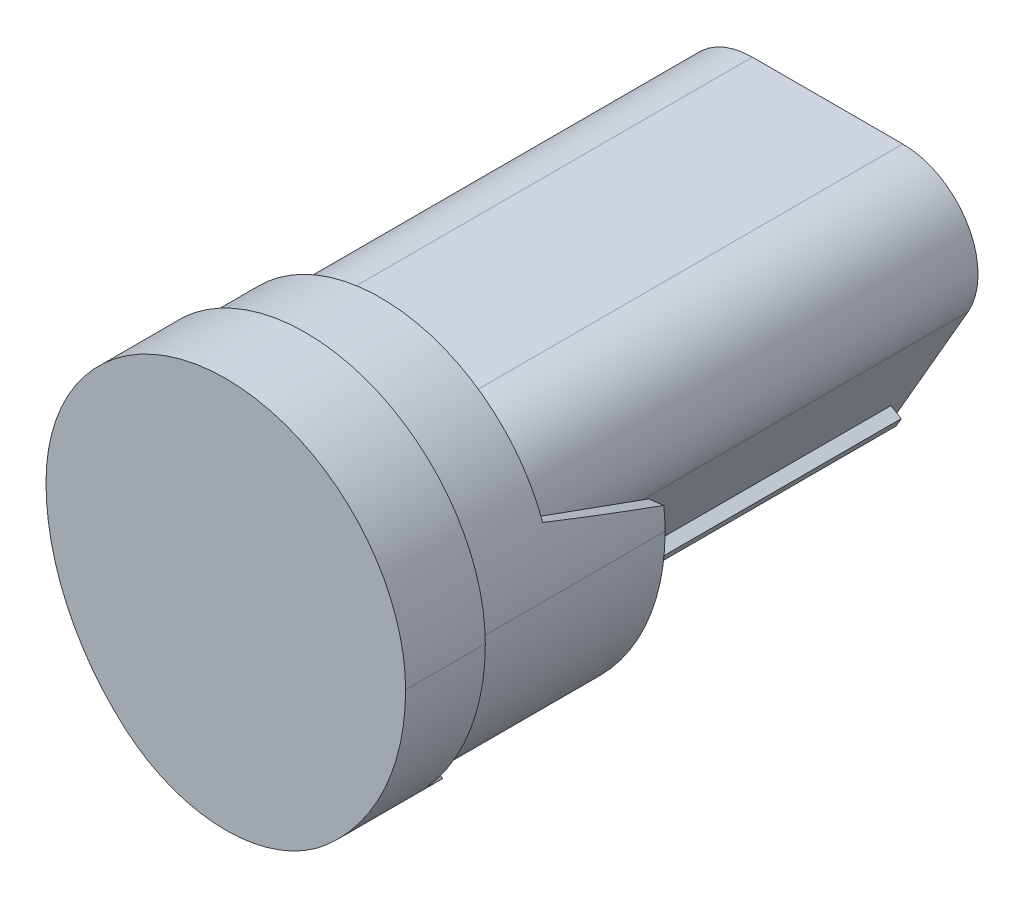
SolidWorks part; units mm, degrees
note: '?' marks a value the reader was unsure of.
ref_plane "Plan de face" through (0, 0, 0) normal (0, 0, 1) x (1, 0, 0)
ref_plane "Plan de dessus" through (0, 0, 0) normal (0, 1, 0) x (1, 0, 0)
ref_plane "Plan de droite" through (0, 0, 0) normal (1, 0, 0) x (0, 0, -1)
ref_axis "Axe1" through (0, 0, 84) along (0, 0, -1)?
sketch "Esquisse1" plane through (0, 0, 0) normal (0, 0, 1) x (1, 0, 0)
  line L0 (-10, 15.7735) -> (10, 15.7735)
  line L1 (-18.6603, 0.7735) -> (-8.6603, -16.547)
  line L2 (8.6603, -16.547) -> (18.6603, 0.7735)
  line L3 (-13.6603, -7.8868) -> (18.6603, 10.7735) construction
  line L4 (13.6603, -7.8868) -> (-18.6603, 10.7735) construction
  line L5 (0, -21.547) -> (0, 15.7735) construction
  line L6 (-20, 2.0501) -> (-20, 16.2695) construction
  line L7 (20, 1.5053) -> (20, 13.4658) construction
  line L8 (445.3732, -108.8997) -> (521.6093, -834.2377) construction
  line L9 (-7.7491, -6.7833) -> (-9.7491, -3.3192) construction
  line L10 (-7.7491, -6.7833) -> (-6.6232, -6.1333) construction
  line L11 (-9.7491, -3.3192) -> (-8.6232, -2.6692) construction
  line L12 (-6.6232, -6.1333) -> (-8.6232, -2.6692) construction
  line L13 (-7.7491, -6.7833) -> (-8.6232, -2.6692) construction
  line L14 (-9.7491, -3.3192) -> (-6.6232, -6.1333) construction
  arc A0 (-8.6603, -16.547) -> (8.6603, -16.547) centre (0, -11.547) ccw
  arc A1 (10, 15.7735) -> (18.6603, 0.7735) centre (10, 5.7735) cw
  arc A2 (-10, 15.7735) -> (-18.6603, 0.7735) centre (-10, 5.7735) ccw
  circle A3 centre (-9.3904, 5.4216) radius 2.9644 construction
  point P15 (0, 0)
  point P25 (-6.5029, -5.9656)
  point P26 (-8.1861, -4.7263)
  point P27 (-8.6603, -2.6051)
  point P28 (0, 0)
  dimension "D1" = 10
  dimension "D2" = 40
  dimension "D3" = 1.3
  dimension "D4" = 4
extrude "Boss.-Extru.1" add sketch "Esquisse1" along normal blind 80
sketch "Esquisse2" plane through (0, 0, 80) normal (0, 0, 1) x (1, 0, 0)
  line L0 (-12681.8859, 1278.2104) -> (-12646.9605, 1282.3837) construction
  line L1 (-242.0525, 250.143) -> (-212.0525, 250.143) construction
  line L2 (30.4051, 69.3804) -> (25.1957, 98.9247) construction
  line L3 (0, -28.2265) -> (0, 23.7735) construction
  line L4 (-7.624, 23.7735) -> (-13.8216, 23.7735) construction
  line L5 (-9.437, -28.2265) -> (-46.2994, -28.2265) construction
  line L6 (-23.9, 23.7735) -> (-23.9, -28.2265) construction
  line L7 (0, 23.7735) -> (0, -28.2265)
  line L9 (0, -28.2265) -> (0, -21.547) construction
  line L10 (0, 23.7735) -> (0, 15.7735) construction
  arc A4 (-8.6603, -16.547) -> (8.6603, -16.547) centre (0, -11.547) ccw construction
  arc A5 (0, 23.7735) -> (-23.9, -0.1265) centre (0, -0.1265) ccw
  arc A6 (-23.9, -0.1265) -> (-13.3729, -23.2265) centre (6.7081, -0.1265) ccw
  arc A7 (-13.3729, -23.2265) -> (0, -28.2265) centre (0, -7.8431) ccw
  point P24 (0, 23.7735)
  point P26 (-13.3729, -23.2265)
  dimension "D3" = 23.9
  dimension "D5" = 8
  dimension "D6" = 5
  dimension "D1" = 35.1738
  dimension "D2" = 30
  dimension "D4" = 52
extrude "Boss.-Extru.2" add sketch "Esquisse2" against normal blind 10.6
mirror "Symétrie1" about plane through (0, 0, 0) normal (1, 0, 0) of "Boss.-Extru.2"
sketch "Esquisse4" plane through (0, 0, 69.4) normal (0, 0, -1) x (-1, 0, 0)
  arc A8 (-22.9, -0.1265) -> (-12.7168, -22.4718) centre (6.7081, -0.1265) ccw
  arc A10 (-12.7168, -22.4718) -> (12.7168, -22.4718) centre (0, -7.8431) ccw
  arc A11 (-12.7168, -22.4718) -> (12.7168, -22.4718) centre (0, -7.8431) ccw
  arc A16 (-22.9, -0.1265) -> (-12.7168, -22.4718) centre (6.7081, -0.1265) ccw
  arc A17 (12.7168, -22.4718) -> (22.9, -0.1265) centre (-6.7081, -0.1265) ccw
  arc A18 (12.7168, -22.4718) -> (22.9, -0.1265) centre (-6.7081, -0.1265) ccw
  arc A19 (22.9, -0.1265) -> (-22.9, -0.1265) centre (0, -0.1265) ccw
  arc A20 (22.9, -0.1265) -> (-22.9, -0.1265) centre (0, -0.1265) ccw
  dimension "D1" = 1
extrude "Boss.-Extru.3" add sketch "Esquisse4" along normal blind 10
sketch "Esquisse6" plane through (0, 0, 69.4) normal (0, 0, -1) x (-1, 0, 0)
  line L0 (0, -28.2265) -> (0, 23.7735) construction
  line L1 (14.75, -21.9532) -> (0, -13.4765)
  line L2 (0, -13.4765) -> (0, -28.2265)
  arc A0 (0, -28.2265) -> (13.3729, -23.2265) centre (0, -7.8431) ccw
  arc A1 (0, -28.2265) -> (13.3729, -23.2265) centre (0, -7.8431) ccw construction
  arc A2 (13.3729, -23.2265) -> (23.9, -0.1265) centre (-6.7081, -0.1265) ccw construction
  arc A3 (13.3729, -23.2265) -> (14.75, -21.9532) centre (-6.7081, -0.1265) ccw
  dimension "D1" = 14.75
  dimension "D2" = 14.75
extrude "Boss.-Extru.4" add sketch "Esquisse6" along normal blind 3.5
mirror "Symétrie2" about plane through (0, 0, 0) normal (1, 0, 0) of "Boss.-Extru.4"
chamfer "Chanfrein1" distance 2 distance2 3.5 2 edges at (-14.2993, -21.6942, 69.4) (14.2993, -21.6942, 69.4)
sketch "Esquisse7" plane through (0, 0, 59.4) normal (0, 0, -1) x (-1, 0, 0)
  line L0 (0, -27.2265) -> (0, 0) construction
  line L2 (10, 15.7735) -> (-10, 15.7735) construction
  line L3 (0, -27.2265) -> (0, 0)
  line L4 (0, 0) -> (22.7156, 2.7735)
  arc A0 (-12.7168, -22.4718) -> (12.7168, -22.4718) centre (0, -7.8431) ccw construction
  arc A1 (0, -27.2265) -> (12.7168, -22.4718) centre (0, -7.8431) ccw
  arc A2 (-12.7168, -22.4718) -> (12.7168, -22.4718) centre (0, -7.8431) ccw construction
  arc A3 (12.7168, -22.4718) -> (22.9, -0.1265) centre (-6.7081, -0.1265) ccw
  arc A4 (12.7168, -22.4718) -> (22.9, -0.1265) centre (-6.7081, -0.1265) ccw construction
  arc A5 (22.9, -0.1265) -> (22.7156, 2.7735) centre (0, -0.1265) ccw
  arc A6 (22.9, -0.1265) -> (-22.9, -0.1265) centre (0, -0.1265) ccw construction
  arc A7 (22.9, -0.1265) -> (-22.9, -0.1265) centre (0, -0.1265) ccw construction
  dimension "D1" = 13
extrude "Boss.-Extru.5" add sketch "Esquisse7" along normal blind 14.9
mirror "Symétrie4" about plane through (0, 0, 0) normal (1, 0, 0) of "Boss.-Extru.5"
chamfer "Chanfrein2" distance 5 distance2 14.9 2 edges at (21.0591, 2.5712, 59.4) (-21.0591, 2.5712, 59.4)
sketch "Esquisse8" plane through (0, 0, 0) normal (0, 0, -1) x (-1, 0, 0)
  line L0 (-18.6603, 0.7735) -> (-8.6603, -16.547) construction
  line L1 (18.6603, 0.7735) -> (8.6603, -16.547) construction
  line L2 (-10, 15.7735) -> (10, 15.7735) construction
  line L3 (-18.6603, 0.7735) -> (-8.6603, -16.547)
  line L4 (18.6603, 0.7735) -> (8.6603, -16.547)
  line L5 (-10, 15.7735) -> (10, 15.7735)
  line L6 (-20.7317, 2.5202) -> (-20.1083, 7.1382)
  line L7 (-16.0835, 13.9607) -> (-12.4653, 16.6493)
  line L8 (20.7317, 2.5202) -> (20.1083, 7.1382)
  line L9 (12.4653, 16.6493) -> (16.0835, 13.9607)
  arc A0 (-10, 15.7735) -> (-18.6603, 0.7735) centre (-10, 5.7735) ccw construction
  arc A1 (-8.6603, -16.547) -> (8.6603, -16.547) centre (0, -11.547) ccw construction
  arc A2 (18.6603, 0.7735) -> (10, 15.7735) centre (10, 5.7735) ccw construction
  arc A3 (-10, 15.7735) -> (-18.6603, 0.7735) centre (-10, 5.7735) ccw
  arc A4 (-8.6603, -16.547) -> (8.6603, -16.547) centre (0, -11.547) ccw
  arc A5 (18.6603, 0.7735) -> (10, 15.7735) centre (10, 5.7735) ccw
  arc A6 (16.0835, 13.9607) -> (20.1083, 7.1382) centre (10, 5.7735) cw
  arc A42 (-12.4653, 16.6493) -> (12.4653, 16.6493) centre (0, -0.1265) cw
  arc A43 (-10, 15.9735) -> (-18.8335, 0.6735) centre (-10, 5.7735) ccw construction
  arc A44 (18.8335, 0.6735) -> (10, 15.9735) centre (10, 5.7735) ccw construction
  arc A45 (-20.1083, 7.1382) -> (-16.0835, 13.9607) centre (-10, 5.7735) cw
  arc A50 (20.7317, 2.5202) -> (19.6527, 6.9857) centre (0, -0.1265) ccw
  arc A51 (20.9, -0.1265) -> (20.7317, 2.5202) centre (0, -0.1265) ccw
  arc A52 (11.4047, -20.9624) -> (20.9, -0.1265) centre (-6.7081, -0.1265) ccw
  arc A53 (-11.4047, -20.9624) -> (11.4047, -20.9624) centre (0, -7.8431) ccw
  arc A54 (-20.9, -0.1265) -> (-11.4047, -20.9624) centre (6.7081, -0.1265) ccw
  arc A55 (-20.7317, 2.5202) -> (-20.9, -0.1265) centre (0, -0.1265) ccw
  arc A56 (-19.6527, 6.9857) -> (-20.7317, 2.5202) centre (0, -0.1265) ccw
  arc A57 (19.6527, 6.9857) -> (-19.6527, 6.9857) centre (0, -0.1265) ccw
  arc A58 (20.7317, 2.5202) -> (19.6527, 6.9857) centre (0, -0.1265) ccw construction
  arc A59 (20.9, -0.1265) -> (20.7317, 2.5202) centre (0, -0.1265) ccw
  arc A60 (11.4047, -20.9624) -> (20.9, -0.1265) centre (-6.7081, -0.1265) ccw
  arc A61 (-11.4047, -20.9624) -> (11.4047, -20.9624) centre (0, -7.8431) ccw
  arc A62 (-20.9, -0.1265) -> (-11.4047, -20.9624) centre (6.7081, -0.1265) ccw
  arc A63 (-20.7317, 2.5202) -> (-20.9, -0.1265) centre (0, -0.1265) ccw
  arc A64 (-19.6527, 6.9857) -> (-20.7317, 2.5202) centre (0, -0.1265) ccw construction
  arc A65 (19.6527, 6.9857) -> (-19.6527, 6.9857) centre (0, -0.1265) ccw construction
  dimension "D2" = 0.2
  dimension "D1" = 2
extrude "Enlèv. mat.-Extru.1" cut sketch "Esquisse8" against normal offset from surface (61.9 mm away) 2.5 up to face at (0, 13.4185, 59.4) offset beyond the face yes
sketch "Esquisse9" plane through (0, 0, 0) normal (0, 0, -1) x (-1, 0, 0)
  line L0 (-10.2144, -13.8552) -> (-11.6, -14.6552)
  line L1 (-8.6603, -16.547) -> (-18.6603, 0.7735) construction
  line L2 (-11.6, -14.6552) -> (-12.3, -13.4428)
  line L3 (-12.3, -13.4428) -> (-10.9144, -12.6428)
  line L4 (-10.9144, -12.6428) -> (-10.2144, -13.8552)
  line L5 (0, 28.6) -> (0, -28.6) construction
  line L6 (10.9144, -12.6428) -> (10.2144, -13.8552)
  line L7 (12.3, -13.4428) -> (10.9144, -12.6428)
  line L8 (11.6, -14.6552) -> (12.3, -13.4428)
  line L9 (10.2144, -13.8552) -> (11.6, -14.6552)
  dimension "D1" = 1.6
  dimension "D2" = 1.4
  dimension "D3" = 24.6
extrude "Boss.-Extru.8" add sketch "Esquisse9" against normal up to next from offset 2.5
